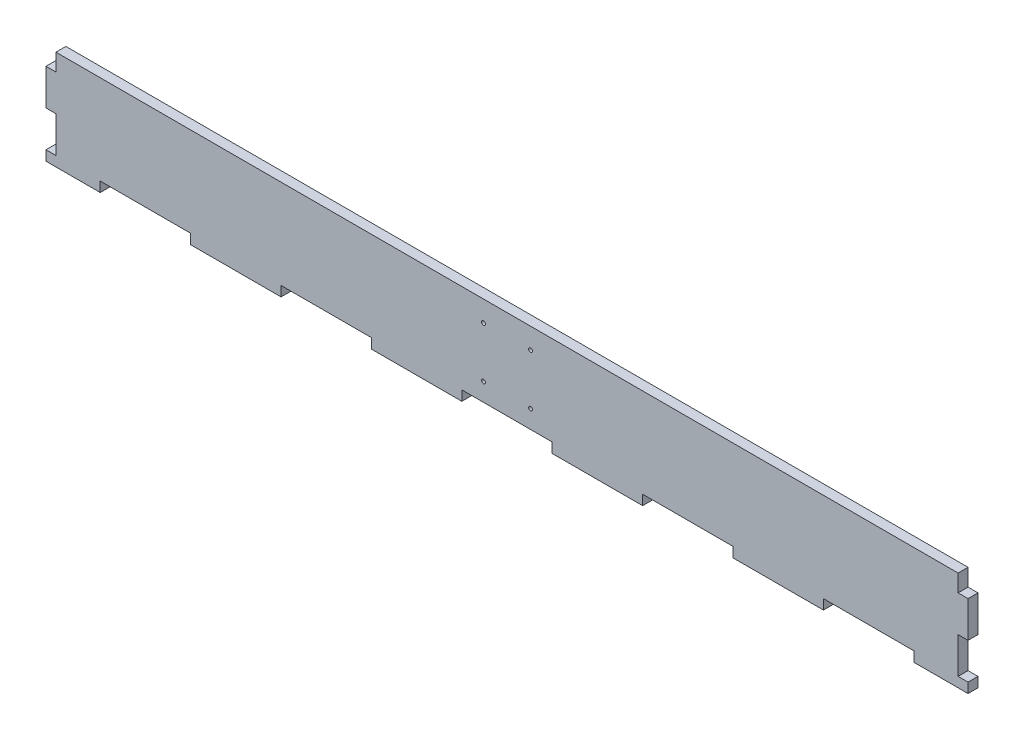
SolidWorks part; units mm, degrees
material "ﾁｰｸ材"
ref_plane "正面" through (0, 0, 0) normal (0, 0, 1) x (1, 0, 0)
ref_plane "平面" through (0, 0, 0) normal (0, 1, 0) x (1, 0, 0)
ref_plane "右側面" through (0, 0, 0) normal (1, 0, 0) x (0, 0, -1)
sketch "ｽｹｯﾁ1" plane through (0, 0, 0) normal (0, 0, 1) x (1, 0, 0)
  line L1 (255, 27.5) -> (-255, 27.5)
  line L2 (255, 27.5) -> (255, -27.5)
  line L3 (255, -27.5) -> (-255, -27.5)
  line L4 (-255, 27.5) -> (-255, -27.5)
  line L5 (255, 27.5) -> (-255, -27.5) construction
  line L6 (255, -27.5) -> (-255, 27.5) construction
  point P0 (0, 0)
  dimension "D1" = 55
  dimension "D2" = 510
extrude "ﾎﾞｽ - 押し出し1" add sketch "ｽｹｯﾁ1" along normal blind 5.5
sketch "ｽｹｯﾁ2" plane through (0, 0, 5.5) normal (0, 0, 1) x (1, 0, 0)
  line L0 (-255, -27.5) -> (255, -27.5) construction
  line L1 (-25, -27.5) -> (25, -27.5)
  line L2 (-25, -27.5) -> (-25, -22)
  line L3 (-25, -22) -> (25, -22)
  line L4 (25, -27.5) -> (25, -22)
  line L5 (-125, -27.5) -> (-75, -27.5)
  line L6 (75, -27.5) -> (125, -27.5)
  line L7 (75, -27.5) -> (75, -22)
  line L8 (75, -22) -> (125, -22)
  line L9 (125, -27.5) -> (125, -22)
  line L10 (-125, -27.5) -> (-125, -22)
  line L11 (-125, -22) -> (-75, -22)
  line L12 (-75, -27.5) -> (-75, -22)
  line L13 (175, -27.5) -> (225, -27.5)
  line L14 (175, -27.5) -> (175, -22)
  line L15 (175, -22) -> (225, -22)
  line L16 (225, -27.5) -> (225, -22)
  line L17 (-225, -27.5) -> (-175, -27.5)
  line L18 (-225, -27.5) -> (-225, -22)
  line L19 (-225, -22) -> (-175, -22)
  line L20 (-175, -27.5) -> (-175, -22)
  point P6 (0, -27.5)
  dimension "D1" = 5.5
  dimension "D2" = 50
  dimension "D3" = 5.5
  dimension "D4" = 50
  dimension "D5" = 50
  dimension "D6" = 50
  dimension "D7" = 5.5
  dimension "D8" = 50
  dimension "D9" = 5.5
  dimension "D10" = 50
  dimension "D11" = 50
  dimension "D12" = 50
  dimension "D13" = 50
extrude "ｶｯﾄ - 押し出し1" cut sketch "ｽｹｯﾁ2" against normal through all
sketch "ｽｹｯﾁ3" plane through (0, 0, 5.5) normal (0, 0, 1) x (1, 0, 0)
  line L0 (255, -27.5) -> (255, 27.5) construction
  line L1 (255, -22) -> (249.5, -22)
  line L2 (255, -22) -> (255, -2)
  line L3 (255, -2) -> (249.5, -2)
  line L4 (249.5, -22) -> (249.5, -2)
  line L5 (225, -27.5) -> (255, -27.5) construction
  line L6 (255, 18) -> (255, 38)
  line L7 (255, 18) -> (249.5, 18)
  line L8 (249.5, 18) -> (249.5, 38)
  line L9 (255, 38) -> (249.5, 38)
  line L10 (0, 0) -> (0, 15.2568) construction
  line L11 (-255, 18) -> (-249.5, 18)
  line L12 (-249.5, 18) -> (-249.5, 38)
  line L13 (-255, 38) -> (-249.5, 38)
  line L14 (-255, 18) -> (-255, 38)
  line L15 (-255, -2) -> (-249.5, -2)
  line L16 (-249.5, -22) -> (-249.5, -2)
  line L17 (-255, -22) -> (-249.5, -22)
  line L18 (-255, -22) -> (-255, -2)
  dimension "D1" = 5.5
  dimension "D2" = 20
  dimension "D3" = 5.5
  dimension "D4" = 2
extrude "ｶｯﾄ - 押し出し2" cut sketch "ｽｹｯﾁ3" against normal through all
sketch "ｽｹｯﾁ4" plane through (0, 0, 5.5) normal (0, 0, 1) x (1, 0, 0)
  circle A0 centre (13, -12) radius 1.05
  circle A1 centre (-13, -12) radius 1.05
  circle A2 centre (-13, 16) radius 1.05
  circle A3 centre (13, 16) radius 1.05
  point P8 (-13, -7.8659)
  point P10 (-13, -11.3059)
  dimension "D1" = 2.1
  dimension "D2" = 13
  dimension "D3" = 13
  dimension "D4" = 16
  dimension "D5" = 12
extrude "ｶｯﾄ - 押し出し3" cut sketch "ｽｹｯﾁ4" against normal through all
